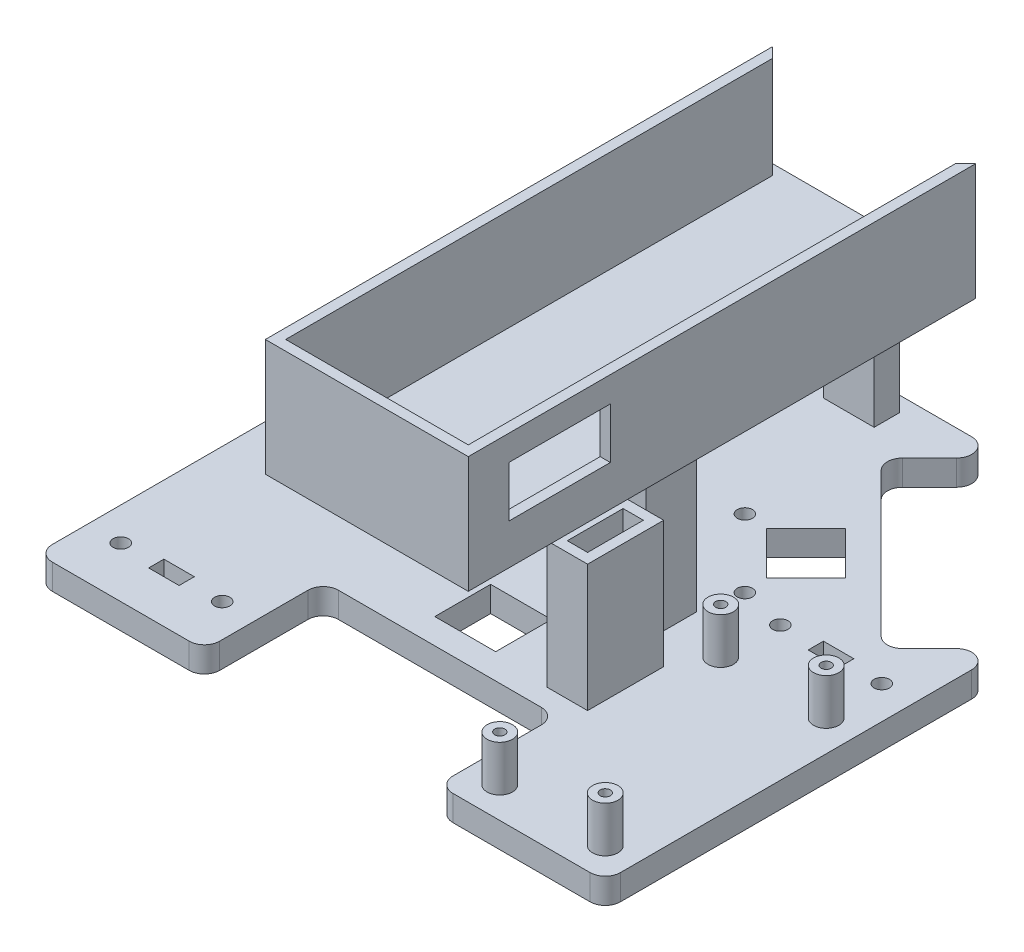
SolidWorks part; units mm, degrees
material "ABS"
ref_plane "Front Plane" through (0, 0, 0) normal (0, 0, 1) x (1, 0, 0)
ref_plane "Top Plane" through (0, 0, 0) normal (0, 1, 0) x (1, 0, 0)
ref_plane "Right Plane" through (0, 0, 0) normal (1, 0, 0) x (0, 0, -1)
sketch "Sketch1" plane through (0, 0, 0) normal (0, 1, 0) x (1, 0, 0)
  line L0 (33.1299, 60) -> (60, 33.1299) construction
  line L1 (-60, 60) -> (60, 60) construction
  line L2 (-60, 60) -> (-60, -60) construction
  line L3 (-60, -60) -> (60, -60) construction
  line L4 (60, 60) -> (60, -60) construction
  line L5 (-60, 60) -> (60, -60) construction
  line L6 (-60, -60) -> (60, 60) construction
  line L7 (-19, -60) -> (19, -60) construction
  line L8 (-19, -60) -> (-19, -36.6) construction
  line L9 (-19, -36.6) -> (19, -36.6) construction
  line L10 (19, -60) -> (19, -36.6) construction
  line L11 (-6, -36.6) -> (6, -36.6) construction
  line L12 (-6, -36.6) -> (-6, -1.6) construction
  line L13 (-6, -1.6) -> (6, -1.6) construction
  line L14 (6, -36.6) -> (6, -1.6) construction
  line L15 (33.1299, 60) -> (16.5836, 43.4537) construction
  line L16 (16.5836, 43.4537) -> (43.4537, 16.5836) construction
  line L17 (43.4537, 16.5836) -> (60, 33.1299) construction
  line L18 (25.776, 34.2613) -> (1.0273, 9.5126) construction
  line L19 (1.0273, 9.5126) -> (9.5126, 1.0273) construction
  line L20 (9.5126, 1.0273) -> (34.2613, 25.776) construction
  line L21 (0, 60) -> (0, -60) construction
  line L22 (7.0377, 20.4727) -> (20.4727, 7.0377) construction
  line L23 (-9.5, -13.6) -> (9.5, -13.6) construction
  line L24 (0, -13.6) -> (0, -36.6) construction
  line L25 (-33.1299, 60) -> (33.1299, 60) construction
  line L26 (33.1299, 60) -> (16.5836, 43.4537) construction
  line L27 (16.5836, 43.4537) -> (43.4537, 16.5836) construction
  line L28 (43.4537, 16.5836) -> (60, 33.1299) construction
  line L29 (60, 33.1299) -> (60, -60) construction
  line L30 (60, -60) -> (19, -60) construction
  line L31 (19, -60) -> (19, -36.6) construction
  line L32 (19, -36.6) -> (-19, -36.6) construction
  line L33 (-19, -60) -> (-19, -36.6) construction
  line L34 (-60, -60) -> (-19, -60) construction
  line L35 (-60, 33.1299) -> (-60, -60) construction
  line L36 (-43.4537, 16.5836) -> (-60, 33.1299) construction
  line L37 (-16.5836, 43.4537) -> (-43.4537, 16.5836) construction
  line L38 (-33.1299, 60) -> (-16.5836, 43.4537) construction
  line L39 (23, -32.6) -> (-23, -32.6)
  line L40 (-23, -56) -> (-23, -32.6)
  line L41 (-56, -56) -> (-23, -56)
  line L42 (-56, 23.4731) -> (-56, -56)
  line L43 (-43.4537, 10.9268) -> (-56, 23.4731)
  line L44 (-10.9268, 43.4537) -> (-43.4537, 10.9268)
  line L45 (-23.4731, 56) -> (-10.9268, 43.4537)
  line L46 (-23.4731, 56) -> (23.4731, 56)
  line L47 (23.4731, 56) -> (10.9268, 43.4537)
  line L48 (10.9268, 43.4537) -> (43.4537, 10.9268)
  line L49 (43.4537, 10.9268) -> (56, 23.4731)
  line L50 (56, 23.4731) -> (56, -56)
  line L51 (56, -56) -> (23, -56)
  line L52 (23, -56) -> (23, -32.6)
  line L53 (19.4121, 27.8974) -> (11.6339, 20.1192)
  line L58 (-6, -16.6) -> (6, -16.6)
  line L59 (-6, -16.6) -> (-6, -27.6)
  line L60 (-6, -27.6) -> (6, -27.6)
  line L61 (6, -16.6) -> (6, -27.6)
  line L62 (11.6339, 20.1192) -> (20.1192, 11.6339)
  line L63 (20.1192, 11.6339) -> (27.8974, 19.4121)
  line L64 (27.8974, 19.4121) -> (19.4121, 27.8974)
  line L65 (-20.1192, 11.6339) -> (-27.8974, 19.4121)
  line L66 (-11.6339, 20.1192) -> (-20.1192, 11.6339)
  line L67 (-19.4121, 27.8974) -> (-11.6339, 20.1192)
  line L68 (-27.8974, 19.4121) -> (-19.4121, 27.8974)
  line L70 (29.105, -6.345) -> (49.895, -6.345) construction
  line L71 (29.105, -6.345) -> (29.105, -49.895) construction
  line L72 (29.105, -49.895) -> (49.895, -49.895) construction
  line L73 (49.895, -6.345) -> (49.895, -49.895) construction
  circle A0 centre (7.0377, 20.4727) radius 1.5
  circle A1 centre (20.4727, 7.0377) radius 1.5
  circle A2 centre (-9.5, -13.6) radius 1.5
  circle A3 centre (9.5, -13.6) radius 1.5
  circle A4 centre (-20.4727, 7.0377) radius 1.5
  circle A5 centre (-7.0377, 20.4727) radius 1.5
  circle A6 centre (29.105, -6.345) radius 1
  circle A7 centre (49.895, -6.345) radius 1
  circle A8 centre (49.895, -49.895) radius 1
  circle A9 centre (29.105, -49.895) radius 1
  point P0 (0, 0)
  point P10 (0, -60)
  point P15 (0, -36.6)
  point P24 (5.2699, 5.2699)
  point P30 (13.7552, 13.7552)
  point P35 (0, -13.6)
  point P77 (39.5, -49.895)
  point P78 (39.5, -56)
  dimension "D11" = 3
  dimension "D12" = 4
  dimension "D18" = 2
  dimension "D1" = 120
  dimension "D2" = 120
  dimension "D3" = 38
  dimension "D4" = 23.4
  dimension "D5" = 12
  dimension "D6" = 35
  dimension "D7" = 19
  dimension "D8" = 45
  dimension "D9" = 23
  dimension "D10" = 23
  dimension "D13" = 9
  dimension "D14" = 11
  dimension "D15" = 9
  dimension "D16" = 20.79
  dimension "D17" = 43.55
extrude "Boss-Extrude1" add sketch "Sketch1" along normal blind 5
fillet "Fillet1" radius 3 14 edges at (23, 2.5, 32.6) (23, 2.5, 56) (56, 2.5, 56) (56, 2.5, -23.4731) (43.4537, 2.5, -10.9268) (10.9268, 2.5, -43.4537) (23.4731, 2.5, -56) (-10.9268, 2.5, -43.4537) (-23.4731, 2.5, -56) (-43.4537, 2.5, -10.9268) (-56, 2.5, -23.4731) (-56, 2.5, 56) (-23, 2.5, 56) (-23, 2.5, 32.6)
sketch "Sketch3" plane through (0, 0, 56) normal (0, 0, 1) x (1, 0, 0)
  line L9 (-26.7, 17.2) -> (-26.7, 5)
  line L11 (-54, 5) -> (-54, 17.2)
  line L12 (-53, 5) -> (-26, 5) construction
  line L13 (-54, 17.2) -> (-49.2, 17.2)
  line L14 (-49.2, 17.2) -> (-49.2, 5)
  line L15 (-49.2, 5) -> (-54, 5)
  line L16 (-51.2, 17.2) -> (-51.2, 19.2)
  line L17 (-51.2, 19.2) -> (-24.7, 19.2)
  line L18 (-37.95, 19.2) -> (-37.95, 17.2)
  line L19 (-26.7, 17.2) -> (-49.2, 17.2)
  line L20 (-21.9, 17.2) -> (-26.7, 17.2)
  line L22 (-49.2, 17.2) -> (-51.2, 17.2) construction
  line L23 (-56, 0) -> (-56, 5) construction
  line L24 (-21.9, 5) -> (-21.9, 17.2)
  line L25 (-26.7, 5) -> (-21.9, 5)
  line L26 (-24.7, 17.2) -> (-24.7, 19.2)
  line L27 (-24.7, 17.2) -> (-24.7, 5)
  line L28 (-24.7, 5) -> (-26.7, 5)
  line L29 (-51.2, 17.2) -> (-51.2, 5)
  line L30 (-51.2, 5) -> (-49.2, 5)
  circle A0 centre (-51.85, 11.1) radius 0.9
  circle A1 centre (-24.05, 11.1) radius 0.9
  point P2 (0, 0)
  point P18 (-54, 11.1)
  line M22 (-26, 5) -> (-53, 5)
  dimension "D5" = 1.8
  dimension "D1" = 2
  dimension "D2" = 4.8
  dimension "D3" = 12.2
  dimension "D4" = 2.65
  dimension "D6" = 2
  dimension "D7" = 11.25
extrude "Boss-Extrude2" add sketch "Sketch3" along normal blind 7.5 from offset 60 contours L13 L29 L14 M22 | L19 L18 L17 L16 L13 | L20 L26 L17 L18 L19 | L27 L20 L9 L25 M22 region at (-25.708, 11.1, 56) region at (-31.325, 18.2, 56) region at (-44.575, 18.2, 56) region at (-50.192, 11.1, 56) offset against normal yes
extrude "Boss-Extrude3" add sketch "Sketch3<4>" against normal blind 2.5 from surface contours L29 L13 L11 L15 A0 | L13 L29 L14 M22 | L27 L20 L9 L25 M22 | L20 L27 L25 L24 A1 region at (-25.708, 11.1, 56) region at (-23.3, 17.0748, 56) region at (-50.192, 11.1, 56) region at (-52.1, 5.1252, 56) starting at face at (-37.95, 11.4333, 3.5)
sketch "Sketch3<4>" plane through (0, 0, 56) normal (0, 0, 1) x (1, 0, 0) same geometry as "Sketch3"
sketch "Sketch4" plane through (0, 5, 0) normal (0, 1, 0) x (1, 0, 0)
  line L0 (29.105, -6.345) -> (49.895, -49.895) construction
  line L1 (29.105, -49.895) -> (49.895, -6.345) construction
  line L2 (39.5, -28.12) -> (39.5, -56) construction
  line L3 (26, -56) -> (53, -56) construction
  line L4 (39.5, -28.12) -> (56, -28.12) construction
  line L5 (56, -53) -> (56, 16.2304) construction
  circle A0 centre (29.105, -6.345) radius 2.5
  circle A1 centre (29.105, -6.345) radius 1
  circle A2 centre (29.105, -49.895) radius 1
  circle A3 centre (29.105, -49.895) radius 2.5
  circle A4 centre (49.895, -49.895) radius 2.5
  circle A5 centre (49.895, -49.895) radius 1
  circle A6 centre (49.895, -6.345) radius 1
  circle A7 centre (49.895, -6.345) radius 2.5
  dimension "D1" = 2
  dimension "D2" = 5
extrude "Boss-Extrude4" add sketch "Sketch4" along normal blind 9
sketch "Sketch5" plane through (0, 5, 0) normal (0, 1, 0) x (1, 0, 0)
  line L0 (-49.5, -46) -> (-29.5, -46) construction
  line L1 (-60, 60) -> (60, 60) construction
  line L2 (-60, 60) -> (-60, -60) construction
  line L3 (-60, -60) -> (60, -60) construction
  line L4 (60, 60) -> (60, -60) construction
  line L5 (-60, 60) -> (60, -60) construction
  line L6 (-60, -60) -> (60, 60) construction
  line L7 (29.5, 5) -> (49.5, 5) construction
  line L8 (-53, -56) -> (-26, -56) construction
  line L9 (26, -56) -> (53, -56) construction
  line L11 (-42.5, -44.5) -> (-36.5, -44.5)
  line L12 (-42.5, -44.5) -> (-42.5, -47.5)
  line L13 (-42.5, -47.5) -> (-36.5, -47.5)
  line L14 (-36.5, -44.5) -> (-36.5, -47.5)
  line L15 (-42.5, -44.5) -> (-36.5, -47.5) construction
  line L16 (-42.5, -47.5) -> (-36.5, -44.5) construction
  line L17 (36.5, 6.5) -> (42.5, 6.5)
  line L18 (36.5, 6.5) -> (36.5, 3.5)
  line L19 (36.5, 3.5) -> (42.5, 3.5)
  line L20 (42.5, 6.5) -> (42.5, 3.5)
  line L21 (36.5, 6.5) -> (42.5, 3.5) construction
  line L22 (36.5, 3.5) -> (42.5, 6.5) construction
  circle A0 centre (-29.5, -46) radius 1.5
  circle A1 centre (-49.5, -46) radius 1.5
  circle A2 centre (29.5, 5) radius 1.5
  circle A3 centre (49.5, 5) radius 1.5
  point P0 (0, 0)
  point P9 (-39.5, -46)
  point P12 (39.5, 5)
  point P16 (-39.5, -56)
  point P20 (39.5, -56)
  point P22 (-39.5, -46)
  point P27 (39.5, 5)
  dimension "D4" = 3
  dimension "D1" = 120
  dimension "D2" = 120
  dimension "D3" = 20
  dimension "D5" = 10
  dimension "D6" = 55
  dimension "D7" = 6
  dimension "D8" = 3
extrude "Cut-Extrude1" cut sketch "Sketch5" against normal through all both and the other way through all
sketch "Sketch6" plane through (0, 5, 0) normal (0, 1, 0) x (1, 0, 0)
  line L0 (16.2304, 56) -> (-16.2304, 56) construction
  line L5 (0, 56) -> (0, 0) construction
  line L6 (-5, 53) -> (5, 53)
  line L7 (-5, 53) -> (-5, 48)
  line L8 (-5, 48) -> (5, 48)
  line L9 (5, 53) -> (5, 48)
  line L10 (-14, -11) -> (-19, -11)
  line L11 (14, -1) -> (19, -1)
  line L12 (14, -1) -> (14, -11)
  line L13 (14, -11) -> (19, -11)
  line L14 (19, -1) -> (19, -11)
  line L15 (-19, -1) -> (-19, -11)
  line L16 (-14, -1) -> (-19, -1)
  line L17 (-14, -1) -> (-14, -11)
  point P6 (0, 53)
  point P7 (0, 56)
  point P11 (14, -6)
  dimension "D1" = 10
  dimension "D2" = 5
  dimension "D3" = 3
  dimension "D4" = 14
  dimension "D5" = 1
extrude "Boss-Extrude5" add sketch "Sketch6" along normal blind 27
sketch "Sketch7" plane through (0, 32, 0) normal (0, 1, 0) x (1, 0, 0)
  line L0 (5, 53) -> (-5, 53) construction
  line L1 (-20, 53) -> (20, 53)
  line L2 (-20, 53) -> (-20, -47)
  line L3 (-20, -47) -> (20, -47)
  line L4 (20, 53) -> (20, -47)
  point P6 (0, 53)
  point P7 (0, 53)
  dimension "D1" = 100
  dimension "D2" = 40
extrude "Boss-Extrude6" add sketch "Sketch7" along normal blind 3
sketch "Sketch8" plane through (0, 35, 0) normal (0, 1, 0) x (1, 0, 0)
  line L0 (-18, 51) -> (-18, -45)
  line L1 (-20, 53) -> (20, 53) construction
  line L2 (-20, 53) -> (-20, -47)
  line L3 (-20, -47) -> (20, -47)
  line L4 (20, 53) -> (20, -47)
  line L5 (-18, -45) -> (18, -45)
  line L6 (18, 51) -> (18, -45)
  line L7 (-18, 51) -> (18, 51) construction
  line L8 (-18, 51) -> (-20, 53)
  line L9 (18, 51) -> (20, 53)
  dimension "D1" = 2
extrude "Boss-Extrude7" add sketch "Sketch8" along normal blind 20
sketch "Sketch9" plane through (20, 0, 0) normal (1, 0, 0) x (0, 0, -1)
  line L0 (-47, 55) -> (53, 55) construction
  line L1 (-39, 50) -> (-19, 50)
  line L2 (-39, 50) -> (-39, 40)
  line L3 (-39, 40) -> (-19, 40)
  line L4 (-19, 50) -> (-19, 40)
  line L5 (-47, 55) -> (-47, 32) construction
  dimension "D1" = 10
  dimension "D2" = 20
  dimension "D3" = 5
  dimension "D4" = 8
extrude "Cut-Extrude2" cut sketch "Sketch9" against normal up to surface (2 mm away) up to face at (18, 45, -3)
sketch "Sketch10" plane through (0, 0, 0) normal (0, 0, 1) x (1, 0, 0)
  line L10 (-5.25, 5) -> (-5.25, 8.5)
  line L12 (-20, 5) -> (20, 5) construction
  line L13 (-5.25, 8.5) -> (5.25, 8.5)
  line L14 (5.25, 8.5) -> (5.25, 5)
  line L15 (5.25, 5) -> (4.25, 5)
  line L16 (4.25, 5) -> (4.25, 7.5)
  line L17 (4.25, 7.5) -> (-4.25, 7.5)
  line L18 (-4.25, 7.5) -> (-4.25, 5)
  line L19 (-4.25, 5) -> (-5.25, 5)
  line L20 (-4.25, 7.5) -> (-4.25, 8.5) construction
  point P10 (0, 7.5)
  dimension "D1" = 1
  dimension "D2" = 2.5
  dimension "D3" = 8.5
extrude "Boss-Extrude8" add sketch "Sketch10" against normal blind 3
sketch "Sketch11" plane through (0, 5, 0) normal (0, 1, 0) x (1, 0, 0)
  line L0 (20, -47) -> (20, 53) construction
  line L1 (17.116, -13.6) -> (25.116, -13.6)
  line L2 (17.116, -13.6) -> (17.116, -28.6)
  line L3 (17.116, -28.6) -> (25.116, -28.6)
  line L4 (25.116, -13.6) -> (25.116, -28.6)
  line L5 (-20, -32.6) -> (20, -32.6) construction
  line L6 (19.116, -15.6) -> (19.116, -26.6)
  line L7 (19.116, -26.6) -> (23.116, -26.6)
  line L8 (23.116, -15.6) -> (23.116, -26.6)
  line L9 (19.116, -15.6) -> (23.116, -15.6)
  dimension "D1" = 2.884
  dimension "D2" = 8
  dimension "D3" = 15
  dimension "D4" = 4
  dimension "D5" = 2
extrude "Boss-Extrude9" add sketch "Sketch11" along normal blind 25
sketch "Sketch12" plane through (17.116, 0, 0) normal (-1, 0, 0) x (0, 0, 1)
  line L0 (13.6, 5) -> (28.6, 5) construction
  line L1 (16.1, 5) -> (26.1, 5)
  line L2 (16.1, 5) -> (16.1, 12)
  line L3 (16.1, 12) -> (26.1, 12)
  line L4 (26.1, 5) -> (26.1, 12)
  point P6 (21.1, 5)
  dimension "D1" = 7
  dimension "D2" = 10
extrude "Cut-Extrude3" cut sketch "Sketch12" against normal blind 4
